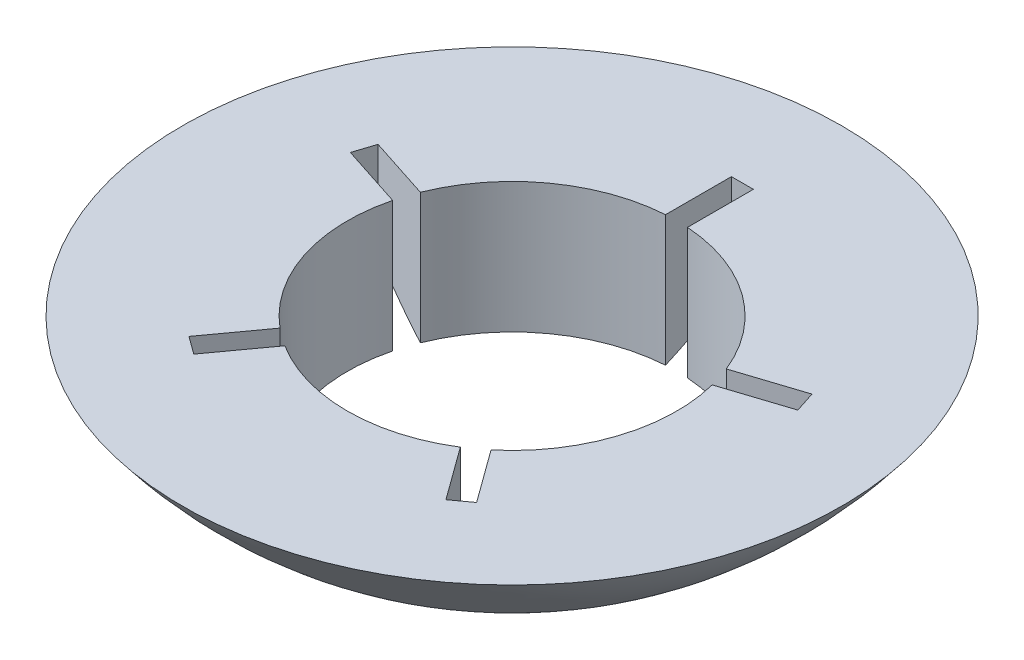
SolidWorks part; units mm, degrees
ref_plane "Piano frontale" through (0, 0, 0) normal (0, 0, 1) x (1, 0, 0)
ref_plane "Piano superiore" through (0, 0, 0) normal (0, 1, 0) x (1, 0, 0)
ref_plane "Piano destro" through (0, 0, 0) normal (1, 0, 0) x (0, 0, -1)
sketch "Schizzo2" plane through (0, 0, 0) normal (0, 0, 1) x (1, 0, 0)
  line L0 (0, 0) -> (3, 0)
  line L1 (3, 0) -> (0, 0)
  line L2 (0, -1.5) -> (0, 0)
  arc A0 (3, 0) -> (0, -1.5) centre (0.0001, 2.2498) cw
  point P5 (0.7254, 0.7992)
  point P6 (0.7254, 0.7992)
  dimension "D3" = 2.2498
  dimension "D1" = 3
  dimension "D2" = 1.5
revolve "Rivoluzione2" add sketch "Schizzo2" angle 360 about L2 region at (1.1626, -0.6117, 0)
ref_plane "Piano1" through (0, -1.5, 0) normal (0, -1, 0) x (-1, 0, 0)
sketch "Schizzo3" plane through (0, -1.5, 0) normal (0, -1, 0) x (-1, 0, 0)
  line L0 (0, 0) -> (0, 3) construction
  line L1 (-0.1, 2.0967) -> (0.1, 2.0967)
  line L2 (-0.1, 2.0967) -> (-0.1, 1.4967)
  line L3 (-0.1, 1.4967) -> (0.1, 1.4967)
  line L4 (0.1, 2.0967) -> (0.1, 1.4967)
  line L5 (-0.1, 2.0967) -> (0.1, 1.4967) construction
  line L6 (-0.1, 1.4967) -> (0.1, 2.0967) construction
  line L7 (0, 0) -> (-2.8532, 0.9271) construction
  line L8 (0, 0) -> (-1.7634, -2.4271) construction
  line L10 (0, 0) -> (1.7634, -2.4271) construction
  line L12 (0, 0) -> (2.8532, 0.9271) construction
  line L14 (-1.981, 0.7488) -> (-2.0428, 0.5586)
  line L15 (-1.981, 0.7488) -> (-1.381, 0.5539)
  line L16 (-2.0428, 0.5586) -> (-1.4428, 0.3636)
  line L17 (-1.381, 0.5539) -> (-1.4428, 0.3636)
  line L18 (-1.981, 0.7488) -> (-1.4428, 0.3636) construction
  line L19 (-2.0428, 0.5586) -> (-1.381, 0.5539) construction
  line L20 (-1.1476, -1.7496) -> (-1.3094, -1.6321)
  line L21 (-1.1476, -1.7496) -> (-0.7949, -1.2642)
  line L22 (-1.3094, -1.6321) -> (-0.9567, -1.1467)
  line L23 (-0.7949, -1.2642) -> (-0.9567, -1.1467)
  line L24 (-1.1476, -1.7496) -> (-0.9567, -1.1467) construction
  line L25 (-1.3094, -1.6321) -> (-0.7949, -1.2642) construction
  line L26 (1.3923, 0.5575) -> (1.4541, 0.3673)
  line L27 (1.3923, 0.5575) -> (1.9629, 0.7429)
  line L28 (1.4541, 0.3673) -> (2.0247, 0.5527)
  line L29 (1.9629, 0.7429) -> (2.0247, 0.5527)
  line L30 (1.3923, 0.5575) -> (2.0247, 0.5527) construction
  line L31 (1.4541, 0.3673) -> (1.9629, 0.7429) construction
  line L32 (0.9567, -1.1467) -> (0.7949, -1.2642)
  line L33 (0.9567, -1.1467) -> (1.3094, -1.6321)
  line L34 (0.7949, -1.2642) -> (1.1476, -1.7496)
  line L35 (1.3094, -1.6321) -> (1.1476, -1.7496)
  line L36 (0.9567, -1.1467) -> (1.1476, -1.7496) construction
  line L37 (0.7949, -1.2642) -> (1.3094, -1.6321) construction
  circle A0 centre (0, 0) radius 1.5
  circle A1 centre (0, 0) radius 3 construction
  point P3 (0, 1.7967)
  point P17 (-1.7119, 0.5562)
  point P18 (1.7085, 0.5551)
  point P19 (-1.0521, -1.4481)
  point P24 (1.0521, -1.4481)
  dimension "D1" = 3
  dimension "D2" = 0.6
  dimension "D3" = 0.2
  dimension "D4" = 0.1
  dimension "D5" = 72
  dimension "D6" = 72
  dimension "D7" = 72
  dimension "D8" = 72
  dimension "D9" = 0.6
  dimension "D10" = 0.2
  dimension "D11" = 0.1
  dimension "D12" = 1.8
  dimension "D13" = 0.6
  dimension "D14" = 0.2
  dimension "D15" = 0.1
  dimension "D16" = 1.79
  dimension "D17" = 0.6
  dimension "D18" = 0.2
  dimension "D19" = 0.1
  dimension "D20" = 1.7964
  dimension "D21" = 0.6
  dimension "D22" = 0.2
  dimension "D23" = 0.1
  dimension "D24" = 1.79
extrude "Taglio-Estrusione3" cut sketch "Schizzo3" against normal through all contours A0 L4 L1 L2 | L17 L15 L14 L16 | L21 L23 L22 L20 | A0 L28 L29 L27 | L35 L33 L32 L34 | A0 region at (0, -1.5, -1.7978) region at (1.7187, -1.5, -0.5584) region at (-1.7097, -1.5, -0.5555) region at (1.0547, -1.5, 1.4517) region at (-1.0547, -1.5, 1.4517)
